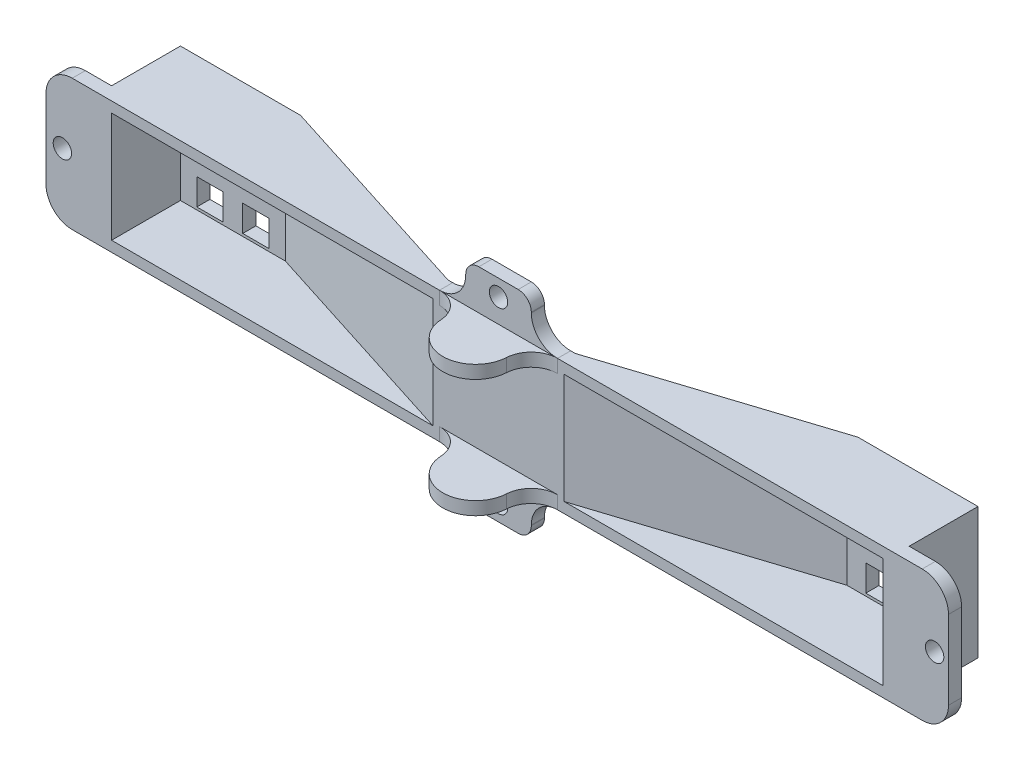
SolidWorks part; units mm, degrees
ref_plane "Piano frontale" through (0, 0, 0) normal (0, 0, 1) x (1, 0, 0)
ref_plane "Piano superiore" through (0, 0, 0) normal (0, 1, 0) x (1, 0, 0)
ref_plane "Piano destro" through (0, 0, 0) normal (1, 0, 0) x (0, 0, -1)
sketch "Schizzo1" plane through (0, 0, 0) normal (0, 1, 0) x (1, 0, 0)
  line L0 (-16, 0) -> (0, 0)
  line L1 (103.6125, -8.5) -> (111.6125, -8.5)
  line L2 (103.6125, 2) -> (103.6125, -8.5)
  line L3 (-16, 0) -> (101.6125, 0) construction
  line L4 (-16, 0) -> (-16, -10.5)
  line L5 (-16, -10.5) -> (33, -10.5) construction
  line L6 (0, 0) -> (33, -10.5)
  line L7 (33, -10.5) -> (53, -10.5)
  line L8 (101.6125, 0) -> (85.6125, 0)
  line L9 (85.6125, 0) -> (53, -10.5)
  line L10 (101.6125, 0) -> (101.6125, -10.5)
  line L11 (101.6125, -10.5) -> (111.6125, -10.5)
  line L12 (-16, -10.5) -> (-26, -10.5)
  line L13 (103.6125, 2) -> (85.2985, 2)
  line L14 (85.2985, 2) -> (52.686, -8.5)
  line L15 (33.3105, -8.5) -> (52.686, -8.5)
  line L16 (0.3105, 2) -> (33.3105, -8.5)
  line L17 (-18, 2) -> (0.3105, 2)
  line L18 (-18, 2) -> (-18, -8.5)
  line L19 (-18, -8.5) -> (-26, -8.5)
  line L20 (-26, -8.5) -> (-26, -10.5)
  line L21 (111.6125, -8.5) -> (111.6125, -10.5)
  dimension "D1" = 16
  dimension "D2" = 2
extrude "Estrusione-Estrusione1" add sketch "Schizzo1" along normal blind 20
sketch "Schizzo2" plane through (0, 0, 0) normal (0, 0, 1) x (1, 0, 0)
  line L0 (-8, 20) -> (-8, 0) construction
  line L1 (-16, 20) -> (0, 20) construction
  line L2 (-16, 0) -> (0, 0) construction
  line L3 (-16, 20) -> (-16, 0) construction
  line L4 (-13.5, 18) -> (-9.5, 18)
  line L5 (-13.5, 18) -> (-13.5, 14)
  line L6 (-13.5, 14) -> (-9.5, 14)
  line L7 (-9.5, 18) -> (-9.5, 14)
  line L8 (-6.5, 18) -> (-2.5, 18)
  line L9 (-2.5, 18) -> (-2.5, 14)
  line L10 (-6.5, 14) -> (-2.5, 14)
  line L11 (-6.5, 18) -> (-6.5, 14)
  line L12 (-6.5, 12) -> (-2.5, 12)
  line L13 (-2.5, 12) -> (-2.5, 8)
  line L14 (-6.5, 8) -> (-2.5, 8)
  line L15 (-6.5, 12) -> (-6.5, 8)
  line L16 (-6.5, 6) -> (-2.5, 6)
  line L17 (-2.5, 6) -> (-2.5, 2)
  line L18 (-6.5, 2) -> (-2.5, 2)
  line L19 (-6.5, 6) -> (-6.5, 2)
  line L20 (-13.5, 12) -> (-9.5, 12)
  line L21 (-9.5, 12) -> (-9.5, 8)
  line L22 (-13.5, 8) -> (-9.5, 8)
  line L23 (-13.5, 12) -> (-13.5, 8)
  line L24 (-13.5, 6) -> (-9.5, 6)
  line L25 (-9.5, 6) -> (-9.5, 2)
  line L26 (-13.5, 2) -> (-9.5, 2)
  line L27 (-13.5, 6) -> (-13.5, 2)
  line L28 (43, 20) -> (43, -2.378) construction
  line L29 (33, 20) -> (53, 20) construction
  line L30 (99.5, 6) -> (99.5, 2)
  line L31 (99.5, 2) -> (95.5, 2)
  line L32 (95.5, 6) -> (95.5, 2)
  line L33 (99.5, 6) -> (95.5, 6)
  line L34 (92.5, 6) -> (92.5, 2)
  line L35 (92.5, 2) -> (88.5, 2)
  line L36 (88.5, 6) -> (88.5, 2)
  line L37 (92.5, 6) -> (88.5, 6)
  line L38 (92.5, 12) -> (92.5, 8)
  line L39 (92.5, 8) -> (88.5, 8)
  line L40 (88.5, 12) -> (88.5, 8)
  line L41 (92.5, 12) -> (88.5, 12)
  line L42 (99.5, 12) -> (99.5, 8)
  line L43 (99.5, 8) -> (95.5, 8)
  line L44 (95.5, 12) -> (95.5, 8)
  line L45 (99.5, 12) -> (95.5, 12)
  line L46 (92.5, 18) -> (92.5, 14)
  line L47 (92.5, 14) -> (88.5, 14)
  line L48 (88.5, 18) -> (88.5, 14)
  line L49 (92.5, 18) -> (88.5, 18)
  line L50 (99.5, 14) -> (95.5, 14)
  line L51 (95.5, 18) -> (95.5, 14)
  line L52 (99.5, 18) -> (95.5, 18)
  line L53 (99.5, 18) -> (99.5, 14)
  dimension "D1" = 2
  dimension "D2" = 2.5
  dimension "D3" = 2
  dimension "D4" = 3
extrude "Taglio-Estrusione2" cut sketch "Schizzo2" against normal blind 20 contours L11 L10 L9 L8 | L4 L7 L6 L5 | L23 L22 L21 L20 | L16 L17 L18 L19 | L13 L14 L15 L12 | L32 L31 L30 L33 | L37 L36 L35 L34 | L41 L40 L39 L38 | L25 L26 L27 L24 | L46 L47 L48 L49 | L50 L51 L52 L53 | L42 L43 L44 L45
sketch "Schizzo3" plane through (0, 0, 10.5) normal (0, 0, 1) x (1, 0, 0)
  line L0 (43, 20) -> (43, -1.0635) construction
  line L1 (33, 20) -> (53, 20) construction
  line L2 (38, 20) -> (38, 26.1024)
  line L3 (38, 26.1024) -> (48, 26.1024)
  line L4 (48, 26.1024) -> (48, 20)
  line L5 (48, 20) -> (38, 20)
  line L6 (33, 10) -> (136.7641, 10) construction
  line L7 (33, 20) -> (33, 0) construction
  line L8 (48, -6.1024) -> (48, 0)
  line L9 (38, -6.1024) -> (48, -6.1024)
  line L10 (38, 0) -> (38, -6.1024)
  line L11 (48, 0) -> (38, 0)
  dimension "D1" = 10
  dimension "D2" = 5
extrude "Estrusione-Estrusione3" add sketch "Schizzo3" against normal blind 2
sketch "Schizzo4" plane through (0, 0, 0) normal (0, -1, 0) x (1, 0, 0)
  line L0 (-16, 0) -> (-16, 10.5)
  line L1 (-16, 10.5) -> (33, 10.5)
  line L2 (33, 10.5) -> (0, 0)
  line L3 (0, 0) -> (-16, 0)
extrude "Estrusione-Estrusione4" add sketch "Schizzo4" against normal blind 1.6
sketch "Schizzo6" plane through (0, 0, 0) normal (0, -1, 0) x (1, 0, 0)
  line L2 (101.6125, 10.5) -> (53, 10.5)
  line L3 (53, 10.5) -> (85.6125, 0) construction
  line L4 (53, 10.5) -> (85.6125, 0)
  line L5 (85.6125, 0) -> (101.6125, 0)
  line L6 (101.6125, 0) -> (101.6125, 10.5)
extrude "Estrusione-Estrusione5" add sketch "Schizzo6" against normal blind 1.6
sketch "Schizzo15" plane through (0, 0, 10.5) normal (0, 0, 1) x (1, 0, 0)
  line L0 (48, 0) -> (38, 0)
  line L1 (48, 0) -> (111.6125, 0) construction
  line L2 (38, 0) -> (38, 2)
  line L3 (38, 2) -> (48, 2)
  line L4 (48, 2) -> (48, 0)
  dimension "D1" = 2
extrude "Estrusione-Estrusione6" add sketch "Schizzo15" along normal blind 8.5
sketch "Schizzo20" plane through (0, 20, 0) normal (0, 1, 0) x (1, 0, 0)
  line L0 (101.6125, -10.5) -> (53, -10.5)
  line L1 (53, -10.5) -> (85.6125, 0) construction
  line L2 (53, -10.5) -> (85.6125, 0)
  line L3 (85.6125, 0) -> (101.6125, 0)
  line L4 (101.6125, 0) -> (101.6125, -10.5)
extrude "Estrusione-Estrusione7" add sketch "Schizzo20" against normal blind 1.6
sketch "Schizzo23" plane through (0, 20, 0) normal (0, 1, 0) x (1, 0, 0)
  line L0 (-16, -10.5) -> (33, -10.5)
  line L1 (0, 0) -> (33, -10.5) construction
  line L2 (33, -10.5) -> (0, 0)
  line L3 (0, 0) -> (-16, 0)
  line L4 (-16, 0) -> (-16, -10.5)
extrude "Estrusione-Estrusione8" add sketch "Schizzo23" against normal blind 1.6
sketch "Schizzo24" plane through (0, 0, 10.5) normal (0, 0, 1) x (1, 0, 0)
  line L0 (111.6125, 10) -> (1.9522, 10) construction
  line L1 (111.6125, 20) -> (111.6125, 0) construction
  line L2 (38, 20) -> (48, 20)
  line L7 (48, 20) -> (48, 18)
  line L8 (48, 18) -> (38, 18)
  line L9 (38, 18) -> (38, 20)
  dimension "D1" = 2
extrude "Estrusione-Estrusione9" add sketch "Schizzo24" along normal blind 8.5
fillet "Raccordo1" 2 edges at (38, 19, 19) (48, 19, 19) type full round first side face at (38, 19, 14.75) second side face at (48, 19, 14.75) middle face at (43, 19, 19)
fillet "Raccordo2" 2 edges at (48, 1, 19) (38, 1, 19) type full round first side face at (48, 1, 14.75) second side face at (38, 1, 14.75) middle face at (43, 1, 19)
fillet "Raccordo3" radius 4 8 edges at (38, 1, 10.5) (48, 1, 10.5) (38, 19, 10.5) (48, 19, 10.5) (-26, 0, 9.5) (-26, 20, 9.5) (111.6125, 0, 9.5) (111.6125, 20, 9.5)
fillet "Raccordo4" radius 4 4 edges at (48, 20, 9.5) (38, 20, 9.5) (38, 0, 9.5) (48, 0, 9.5)
fillet "Raccordo6" radius 2 4 edges at (38, 26.1024, 9.5) (48, 26.1024, 9.5) (38, -6.1024, 9.5) (48, -6.1024, 9.5)
sketch "Schizzo26" plane through (0, 0, 0) normal (0, -1, 0) x (-1, 0, 0)
  line L0 (18, -8.5) -> (-103.6125, -8.5) construction
sketch "Schizzo27" plane through (0, 0, 8.5) normal (0, 0, -1) x (-1, 0, 0)
  line L0 (-43, -6.1024) -> (-43, 26.1024) construction
  line L1 (-40, -6.1024) -> (-46, -6.1024) construction
  line L2 (-46, 26.1024) -> (-40, 26.1024) construction
  circle A0 centre (-43, 10) radius 3.5432
extrude "Taglio-Estrusione5" cut sketch "Schizzo28" against normal blind 10
sketch "Schizzo28" plane through (42.2306, 213.6, 10.5) normal (0, 0, 1) x (1, 0, 0)
  line L0 (0.7694, -203.6) -> (19.6422, -203.6) construction
  circle A0 centre (0.7694, -187.4976) radius 2.5 construction
  circle A1 centre (0.7694, -189.9976) radius 1.4
  circle A2 centre (0.7694, -219.7024) radius 2.5 construction
  circle A3 centre (0.7694, -217.2024) radius 1.4
extrude "Taglio-Estrusione6" cut sketch "Schizzo29" against normal blind 10
sketch "Schizzo29" plane through (42.2306, 213.6, 10.5) normal (0, 0, 1) x (1, 0, 0)
  line L0 (-68.2306, -203.6) -> (0.7694, -203.6) construction
  line L2 (0.7694, -203.6) -> (0.7694, -211.5418) construction
  circle A0 centre (-68.2306, -203.6) radius 2.5 construction
  circle A1 centre (-65.7306, -203.6) radius 1.4
  circle A2 centre (69.7694, -203.6) radius 2.5 construction
  circle A3 centre (67.2694, -203.6) radius 1.4
